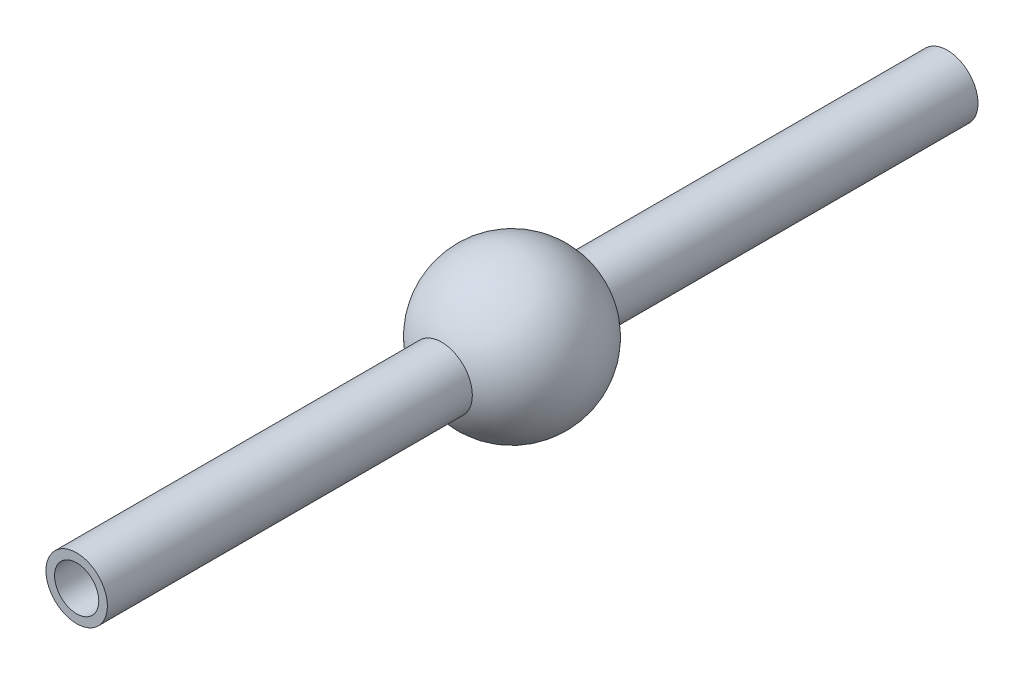
SolidWorks part; units mm, degrees
ref_plane "Front Plane" through (0, 0, 0) normal (0, 0, 1) x (1, 0, 0)
ref_plane "Top Plane" through (0, 0, 0) normal (0, 1, 0) x (1, 0, 0)
ref_plane "Right Plane" through (0, 0, 0) normal (1, 0, 0) x (0, 0, -1)
sketch "Sketch3" plane through (0, 0, 0) normal (0, 1, 0) x (1, 0, 0)
  line L0 (0, -7.935) -> (0, 7.935)
  line L1 (0, 12.4381) -> (0, -14.8873) construction
  arc A0 (0, 7.935) -> (0, -7.935) centre (0, 0) ccw
  dimension "D1" = 15.87
revolve "Revolve3" add sketch "Sketch3" angle 360 about L1
sketch "Sketch4" plane through (0, 0, 0) normal (0, 0, 1) x (1, 0, 0)
  circle A0 centre (0, 0) radius 3.175
  dimension "D1" = 6.35
extrude "Cut-Extrude1" cut sketch "Sketch4" against normal through all and the other way through all
sketch "Sketch5" plane through (0, 0, 0) normal (0, 0, 1) x (1, 0, 0)
  circle A0 centre (0, 0) radius 3.175
  circle A1 centre (0, 0) radius 2.286
  dimension "D1" = 4.572
  dimension "D2" = 6.35
extrude "Boss-Extrude1" add sketch "Sketch5" along normal blind 45 and the other way blind 45
